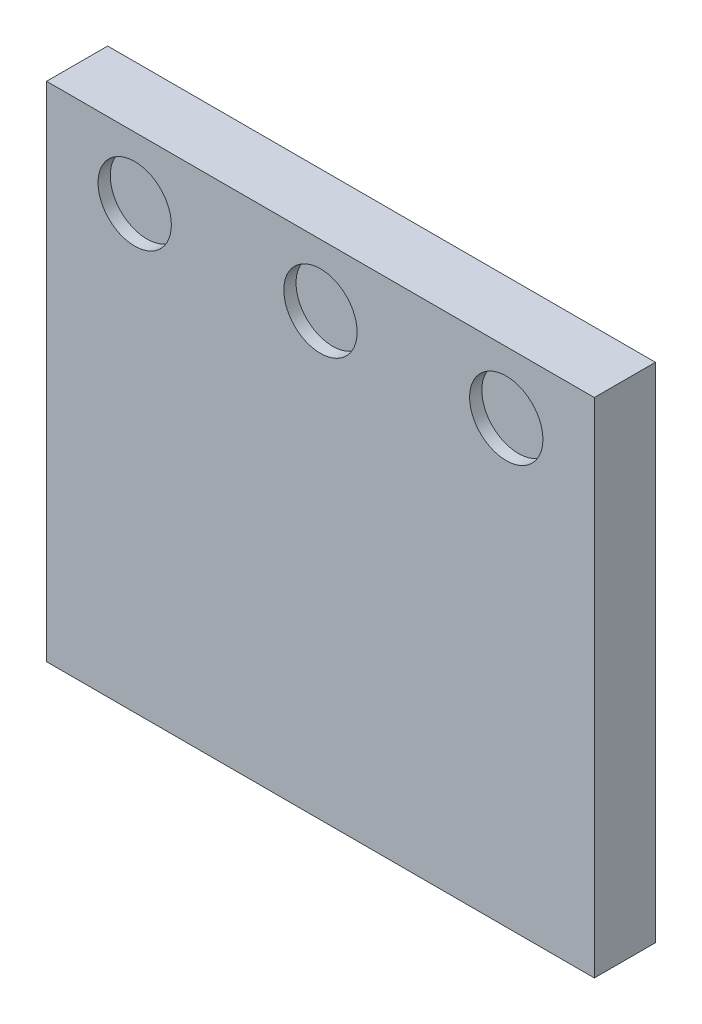
SolidWorks part; units mm, degrees
ref_plane "前视基准面" through (0, 0, 0) normal (0, 0, 1) x (1, 0, 0)
ref_plane "上视基准面" through (0, 0, 0) normal (0, 1, 0) x (1, 0, 0)
ref_plane "右视基准面" through (0, 0, 0) normal (1, 0, 0) x (0, 0, -1)
sketch "草图1" plane through (0, 0, 0) normal (0, 0, 1) x (1, 0, 0)
  line L1 (-44.8378, 41.1484) -> (44.8378, 41.1484)
  line L2 (-44.8378, 41.1484) -> (-44.8378, -41.1484)
  line L3 (-44.8378, -41.1484) -> (44.8378, -41.1484)
  line L4 (44.8378, 41.1484) -> (44.8378, -41.1484)
  line L5 (-44.8378, 41.1484) -> (44.8378, -41.1484) construction
  line L6 (-44.8378, -41.1484) -> (44.8378, 41.1484) construction
  point P0 (0, 0)
extrude "凸台-拉伸1" add sketch "草图1" along normal blind 10
sketch "草图3" plane through (0, 0, 10) normal (0, 0, 1) x (1, 0, 0)
  line L0 (0, -5.5) -> (0, 5.5) construction
  circle A0 centre (-30.4118, 30.9893) radius 6
  circle A1 centre (30.4118, 30.9893) radius 6
extrude "切除-拉伸1" cut sketch "草图3" against normal blind 2
ref_point "A_IN"
ref_point "C_IN"
ref_axis "基准轴1" through (-30.4118, 30.9893, 10) along (1, 0, 0)
sketch "草图4" plane through (0, 0, 10) normal (0, 0, 1) x (1, 0, 0)
  line L0 (0, -5.5) -> (0, 5.5) construction
  line L1 (-30.4118, 30.9893) -> (30.4118, 30.9893) construction
  circle A0 centre (0, 30.9893) radius 6
extrude "切除-拉伸2" cut sketch "草图4" against normal blind 2
ref_point "B_IN"
